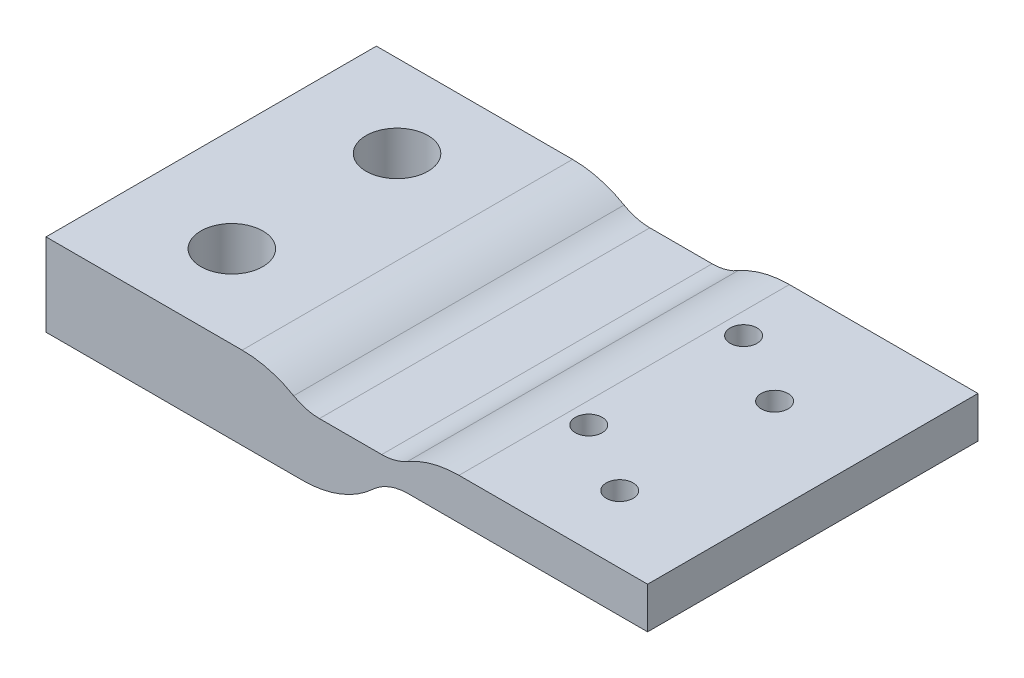
SolidWorks part; units mm, degrees
ref_plane "Front Plane" through (0, 0, 0) normal (0, 0, 1) x (1, 0, 0)
ref_plane "Top Plane" through (0, 0, 0) normal (0, 1, 0) x (1, 0, 0)
ref_plane "Right Plane" through (0, 0, 0) normal (1, 0, 0) x (0, 0, -1)
sketch "Sketch1" plane through (0, 0, 0) normal (0, 1, 0) x (1, 0, 0)
  line L0 (0, 16) -> (0, 7) construction
  line L1 (10.6667, 16) -> (-10.6667, 16)
  line L2 (10.6667, 16) -> (10.6667, -16)
  line L3 (10.6667, -16) -> (-10.6667, -16)
  line L4 (-10.6667, 16) -> (-10.6667, -16)
  line L5 (10.6667, 16) -> (-10.6667, -16) construction
  line L6 (10.6667, -16) -> (-10.6667, 16) construction
  line L7 (0, -16) -> (0, -8) construction
  point P0 (0, 0)
extrude "Boss-Extrude1" add sketch "Sketch1" along normal blind 5
sketch "Sketch2" plane through (0, 0, 0) normal (0, 1, 0) x (1, 0, 0)
  line L0 (10, 16) -> (47.6, 16)
  line L1 (10, 16) -> (10, -16)
  line L2 (10, -16) -> (47.6, -16)
  line L3 (47.6, -16) -> (47.6, 16)
  line L4 (24, 0) -> (10.6667, 0) construction
  line L10 (10.6667, -16) -> (10.6667, 16) construction
  line L12 (47.6, 0) -> (24, 0) construction
  point P2 (19.177, 0)
  point P3 (19.177, 0)
extrude "Boss-Extrude2" add sketch "Sketch2" along normal blind 5
sketch "Sketch7" plane through (0, 0, 0) normal (0, 1, 0) x (1, 0, 0)
  line L0 (34.9, 0) -> (47.6, 0) construction
  line L1 (47.6, -16) -> (47.6, 16) construction
  line L2 (47.6, 16) -> (34.9, 16) construction
  line L6 (34.9, -16) -> (34.9, 16) construction
  line L8 (-10.6667, -16) -> (47.6, -16) construction
  line L21 (47.6, 16) -> (-10.6667, 16) construction
  line L22 (34.9, -9.5) -> (38.4, -9.5) construction
  line L23 (34.9, -5.5) -> (31.4, -5.5) construction
  line L24 (34.9, 5.5) -> (38.4, 5.5) construction
  line L25 (34.9, 9.5) -> (31.4, 9.5) construction
  circle A4 centre (38.4, -9.5) radius 1.3
  circle A5 centre (31.4, -5.5) radius 1.3
  circle A6 centre (38.4, 5.5) radius 1.3
  circle A7 centre (31.4, 9.5) radius 1.3
extrude "Cut-Extrude2" cut sketch "Sketch7" along normal blind 10
sketch "Sketch8" plane through (0, 0, 0) normal (0, 0, 1) x (1, 0, 0)
  line L0 (-10.6667, 5) -> (14.3333, 5) construction
  line L5 (47.6, 0) -> (22.2, 0)
  line L6 (47.6, 0) -> (47.6, 1)
  line L11 (47.6, 1) -> (22.2, 1)
  line L12 (22.2, 0) -> (22.2, 1)
  line L13 (-10.6667, 5) -> (47.6, 5) construction
  line L15 (14.3333, 5) -> (23.3333, 5)
  line L16 (14.3333, 5) -> (14.3333, 3)
  line L17 (14.3333, 3) -> (23.3333, 3)
  line L18 (23.3333, 5) -> (23.3333, 3)
extrude "Cut-Extrude3" cut sketch "Sketch8" against normal through all both and the other way through all
sketch "Sketch9" plane through (0, 0, 0) normal (0, 1, 0) x (1, 0, 0)
  line L1 (-10.6667, 16) -> (22.2, 16)
  line L2 (-10.6667, 16) -> (-10.6667, -16)
  line L3 (-10.6667, -16) -> (22.2, -16)
  line L4 (22.2, 16) -> (22.2, -16)
extrude "Boss-Extrude3" add sketch "Sketch9" against normal blind 3
sketch "Sketch10" plane through (0, 0, 0) normal (0, 1, 0) x (1, 0, 0)
  line L0 (-10.6667, 16) -> (9.3333, 16) construction
  line L1 (47.6, 16) -> (23.3333, 16) construction
  line L2 (-0.6667, 16) -> (-0.6667, 8) construction
  line L3 (-0.6667, -16) -> (-0.6667, -8) construction
  line L4 (-10.6667, -16) -> (14.3333, -16) construction
  circle A0 centre (-0.6667, 8) radius 3
  circle A1 centre (-0.6667, -8) radius 3
extrude "Cut-Extrude4" cut sketch "Sketch10" against normal through all both and the other way through all
sketch "Sketch11" plane through (0, 0, 0) normal (0, 1, 0) x (1, 0, 0)
  line L0 (-5.8667, 8) -> (-5.8667, -8)
  line L1 (4.5333, 8) -> (4.5333, -8)
  arc A0 (-5.8667, -8) -> (4.5333, -8) centre (-0.6667, -8) ccw
  arc A1 (4.5333, 8) -> (-5.8667, 8) centre (-0.6667, 8) ccw
extrude "Cut-Extrude5" cut sketch "Sketch11" against normal blind 8
fillet "Fillet8" radius 3 4 edges at (-0.6667, -3, -13.2) (-0.6667, -3, 13.2) (-5.8667, -3, 0) (4.5333, -3, 0)
fillet "Fillet9" radius 10 3 edges at (23.3333, 5, 0) (14.3333, 5, 0) (22.2, -3, 0)
fillet "Fillet10" radius 5 3 edges at (22.2, 1, 0) (23.3333, 3, 0) (14.3333, 3, 0)
